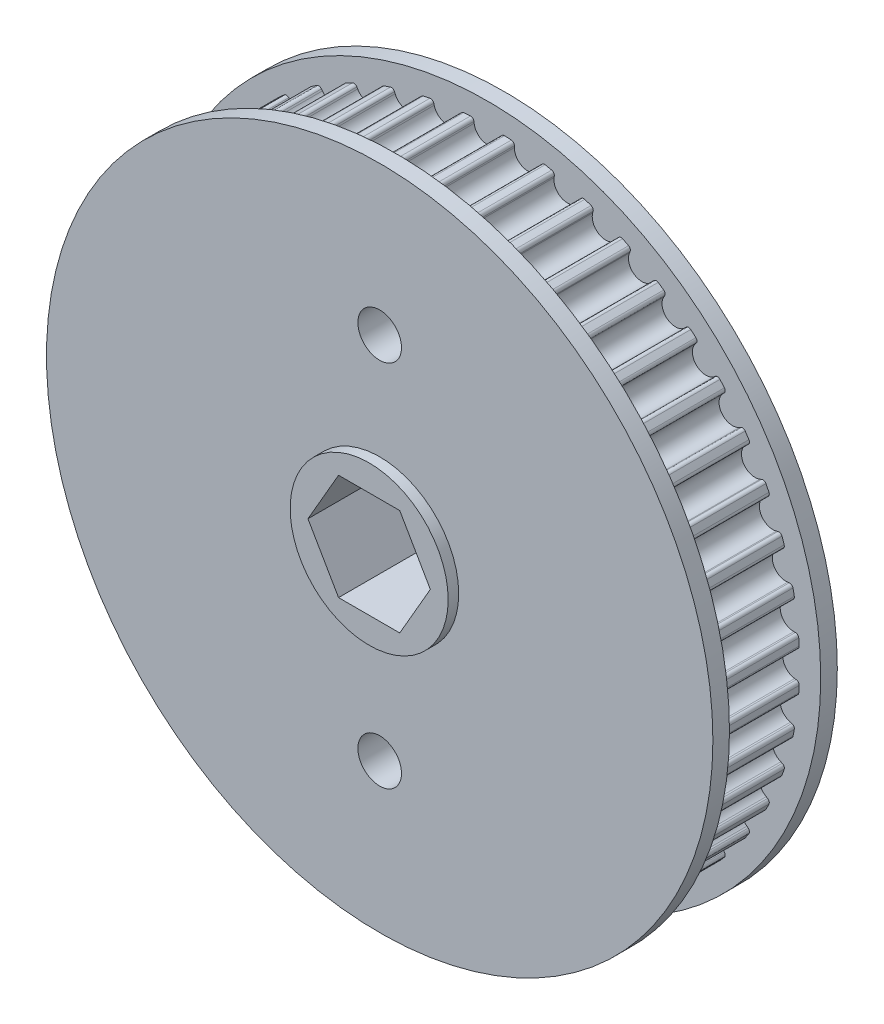
SolidWorks part; units mm, degrees
material "ABS"
ref_plane "Front Plane" through (0, 0, 0) normal (0, 0, 1) x (1, 0, 0)
ref_plane "Top Plane" through (0, 0, 0) normal (0, 1, 0) x (1, 0, 0)
ref_plane "Right Plane" through (0, 0, 0) normal (1, 0, 0) x (0, 0, -1)
sketch "Sketch2" plane through (0, 0, 0) normal (0, 0, 1) x (1, 0, 0)
  circle A0 centre (0, 0) radius 37.6245
  dimension "D1" = 75.2489
extrude "pulley" add sketch "Sketch2" along normal mid plane 11
sketch "tooth" plane through (0, 0, 0) normal (0, 0, 1) x (1, 0, 0)
  line L0 (0, 0) -> (0, 37.2245) construction
  line L1 (4.9887, 36.8887) -> (0, 37.2245) construction
  line L2 (4.9887, 36.8887) -> (0, 0) construction
  line L3 (-2.1327, 41.2601) -> (-1.6129, 37.0264)
  line L6 (2.1327, 41.2601) -> (1.6129, 37.0264)
  line L7 (-2.1327, 41.2601) -> (2.1327, 41.2601)
  arc A1 (-1.6129, 37.0264) -> (1.6129, 37.0264) centre (0, 37.2245) ccw
  arc A2 (0, 37.2245) -> (4.9887, 36.8887) centre (0, 0) cw construction
  circle A3 centre (4.9887, 36.8887) radius 1.625 construction
  dimension "D1" = 37.2245
  dimension "D2" = 3.25
  dimension "D3" = 5
  dimension "D4" = 7.702
  dimension "D5" = 14
extrude "cut tooth" cut sketch "tooth" against normal mid plane 11
fillet "blend tooth" radius 0.4 2 edges at (1.6817, 37.5869, 0) (-1.6817, 37.5869, 0)
pattern_circular "tooth pattern" count 48 over 360 about axis through (0, 0, 5.5) along (0, 0, -1) of "cut tooth", "blend tooth"
sketch "Sketch3" plane through (0, 0, 0) normal (0, 0, 1) x (1, 0, 0)
  circle A0 centre (0, 0) radius 40.1645
  circle A1 centre (0, 0) radius 37.6245 construction
  dimension "D1" = 2.54
extrude "sidewall" add sketch "Sketch3" along normal blind 2 from offset 5.5
mirror "mirror sidewall" about plane through (0, 0, 0) normal (0, 0, 1) of "sidewall"
chamfer "sidewall chamfer" [suppressed] distance 2.4 angle 10
sketch "Sketch5" plane through (0, 0, 0) normal (0, 0, 1) x (1, 0, 0)
  circle A0 centre (0, 0) radius 9.525
  dimension "D1" = 19.05
extrude "bearing spacer (Manual Suppress)" add sketch "Sketch5" along normal blind 8.77 and the other way blind 8.77
sketch "Sketch4" plane through (0, 0, 0) normal (0, 0, 1) x (1, 0, 0)
  line L1 (3.6882, 6.3881) -> (-3.6882, 6.3881)
  line L2 (-3.6882, 6.3881) -> (-7.3763, 0)
  line L3 (-7.3763, 0) -> (-3.6882, -6.3881)
  line L4 (-3.6882, -6.3881) -> (3.6882, -6.3881)
  line L5 (3.6882, -6.3881) -> (7.3763, 0)
  line L6 (7.3763, 0) -> (3.6882, 6.3881)
  circle A0 centre (0, 0) radius 6.3881 construction
  dimension "D1" = 12.7762
extrude "hex shaft" cut sketch "Sketch4" against normal mid plane 127
chamfer "chamfers" [suppressed] distance 0.254 angle 45
sketch "SK-VersaCut" plane through (0, 0, 0) normal (0, 0, 1) x (1, 0, 0)
  line B0 (6.3387, 23.6565) -> (5.299, 19.7762)
  line B1 (14.4772, 14.4772) -> (17.3177, 17.3177)
  line B2 (23.6565, 6.3387) -> (19.7762, 5.299)
  line B3 (19.7762, -5.299) -> (23.6565, -6.3387)
  line B4 (17.3177, -17.3177) -> (14.4772, -14.4772)
  line B5 (5.299, -19.7762) -> (6.3387, -23.6565)
  line B6 (-6.3387, -23.6565) -> (-5.299, -19.7762)
  line B7 (-14.4772, -14.4772) -> (-17.3177, -17.3177)
  line B8 (-23.6565, -6.3387) -> (-19.7762, -5.299)
  line B9 (-19.7762, 5.299) -> (-23.6565, 6.3387)
  line B10 (-17.3177, 17.3177) -> (-14.4772, 14.4772)
  line B11 (-5.299, 19.7762) -> (-6.3387, 23.6565)
  circle B12 centre (0, 23.8125) radius 2.2479
  arc B13 (5.9535, 18.5765) -> (13.1109, 14.4442) centre (0, 0) cw
  arc B14 (7.5904, 24.3458) -> (17.2889, 18.7464) centre (0, 0) cw
  arc B15 (5.9535, 18.5765) -> (5.299, 19.7762) centre (6.2559, 19.5198) cw
  arc B16 (13.1109, 14.4442) -> (14.4772, 14.4772) centre (13.7767, 15.1777) ccw
  arc B17 (17.2889, 18.7464) -> (17.3177, 17.3177) centre (16.6173, 18.0182) cw
  arc B18 (7.5904, 24.3458) -> (6.3387, 23.6565) centre (7.2956, 23.4001) ccw
  circle B19 centre (20.6222, 11.9062) radius 2.2479
  arc B20 (19.0645, 4.1323) -> (19.0645, -4.1323) centre (0, 0) cw
  arc B21 (24.8793, 5.5994) -> (24.8793, -5.5994) centre (0, 0) cw
  arc B22 (19.0645, 4.1323) -> (19.7762, 5.299) centre (20.0326, 4.3422) cw
  arc B23 (19.0645, -4.1323) -> (19.7762, -5.299) centre (20.0326, -4.3422) ccw
  arc B24 (24.8793, -5.5994) -> (23.6565, -6.3387) centre (23.9129, -5.3819) cw
  arc B25 (24.8793, 5.5994) -> (23.6565, 6.3387) centre (23.9129, 5.3819) ccw
  circle B26 centre (20.6222, -11.9063) radius 2.2479
  arc B27 (13.1109, -14.4442) -> (5.9535, -18.5765) centre (0, 0) cw
  arc B28 (17.2889, -18.7464) -> (7.5904, -24.3458) centre (0, 0) cw
  arc B29 (13.1109, -14.4442) -> (14.4772, -14.4772) centre (13.7767, -15.1777) cw
  arc B30 (5.9535, -18.5765) -> (5.299, -19.7762) centre (6.2559, -19.5198) ccw
  arc B31 (7.5904, -24.3458) -> (6.3387, -23.6565) centre (7.2956, -23.4001) cw
  arc B32 (17.2889, -18.7464) -> (17.3177, -17.3177) centre (16.6173, -18.0182) ccw
  circle B33 centre (0, -23.8125) radius 2.2479
  arc B34 (-5.9535, -18.5765) -> (-13.1109, -14.4442) centre (0, 0) cw
  arc B35 (-7.5904, -24.3458) -> (-17.2889, -18.7464) centre (0, 0) cw
  arc B36 (-5.9535, -18.5765) -> (-5.299, -19.7762) centre (-6.2559, -19.5198) cw
  arc B37 (-13.1109, -14.4442) -> (-14.4772, -14.4772) centre (-13.7767, -15.1777) ccw
  arc B38 (-17.2889, -18.7464) -> (-17.3177, -17.3177) centre (-16.6173, -18.0182) cw
  arc B39 (-7.5904, -24.3458) -> (-6.3387, -23.6565) centre (-7.2956, -23.4001) ccw
  circle B40 centre (-20.6222, -11.9063) radius 2.2479
  arc B41 (-19.0645, -4.1323) -> (-19.0645, 4.1323) centre (0, 0) cw
  arc B42 (-24.8793, -5.5994) -> (-24.8793, 5.5994) centre (0, 0) cw
  arc B43 (-19.0645, -4.1323) -> (-19.7762, -5.299) centre (-20.0326, -4.3422) cw
  arc B44 (-19.0645, 4.1323) -> (-19.7762, 5.299) centre (-20.0326, 4.3422) ccw
  arc B45 (-24.8793, 5.5994) -> (-23.6565, 6.3387) centre (-23.9129, 5.3819) cw
  arc B46 (-24.8793, -5.5994) -> (-23.6565, -6.3387) centre (-23.9129, -5.3819) ccw
  circle B47 centre (-20.6222, 11.9063) radius 2.2479
  arc B48 (-13.1109, 14.4442) -> (-5.9535, 18.5765) centre (0, 0) cw
  arc B49 (-17.2889, 18.7464) -> (-7.5904, 24.3458) centre (0, 0) cw
  arc B50 (-13.1109, 14.4442) -> (-14.4772, 14.4772) centre (-13.7767, 15.1777) cw
  arc B51 (-5.9535, 18.5765) -> (-5.299, 19.7762) centre (-6.2559, 19.5198) ccw
  arc B52 (-7.5904, 24.3458) -> (-6.3387, 23.6565) centre (-7.2956, 23.4001) cw
  arc B53 (-17.2889, 18.7464) -> (-17.3177, 17.3177) centre (-16.6173, 18.0182) ccw
sketch_block_instance "VersaKey-1"
sketch_block "Block1" parameters "D1"=47.625, "D2"=4.4958, "D3"=19.5072, "D4"=25.5016, "D6"=0.9906, "D5"=30
extrude "VersaKey (Manual Suppress)" [suppressed] cut sketch "SK-VersaCut" against normal through all both and the other way through all
sketch "Lightening Holes" plane through (0, 0, 0) normal (0, 0, 1) x (1, 0, 0)
  line L0 (-13.5587, 28.5643) -> (-3.9521, 11.9253)
  line L1 (3.9521, 11.9253) -> (13.5587, 28.5643)
  line L14 (0, 0) -> (-3.6662, 6.35) construction
  line L15 (0, 0) -> (0, 6.35) construction
  line L24 (0, 0) -> (3.6662, 6.35) construction
  line L25 (0, 6.35) -> (-3.6662, 6.35) construction
  line L26 (0, 6.35) -> (3.6662, 6.35) construction
  line L27 (-3.0943, 11.43) -> (3.0943, 11.43)
  line L28 (0, 6.35) -> (0, 11.43) construction
  line L29 (17.9581, 26.0243) -> (8.3515, 9.3853)
  line L30 (8.3515, 8.3947) -> (11.4458, 3.0353)
  line L31 (12.3037, 2.54) -> (31.5167, 2.54)
  line L32 (31.5167, -2.54) -> (12.3037, -2.54)
  line L33 (11.4458, -3.0353) -> (8.3515, -8.3947)
  line L34 (8.3515, -9.3853) -> (17.9581, -26.0243)
  line L35 (13.5587, -28.5643) -> (3.9521, -11.9253)
  line L36 (3.0943, -11.43) -> (-3.0943, -11.43)
  line L37 (-3.9521, -11.9253) -> (-13.5587, -28.5643)
  line L38 (-17.9581, -26.0243) -> (-8.3515, -9.3853)
  line L39 (-8.3515, -8.3947) -> (-11.4458, -3.0353)
  line L40 (-12.3037, -2.54) -> (-31.5167, -2.54)
  line L41 (-31.5167, 2.54) -> (-12.3037, 2.54)
  line L42 (-11.4458, 3.0353) -> (-8.3515, 8.3947)
  line L43 (-8.3515, 9.3853) -> (-17.9581, 26.0243)
  arc A3 (-13.0975, 29.9673) -> (13.0975, 29.9673) centre (0, 0) cw
  arc A4 (-3.0943, 11.43) -> (-3.9521, 11.9253) centre (-3.0943, 12.4206) cw
  arc A5 (3.0943, 11.43) -> (3.9521, 11.9253) centre (3.0943, 12.4206) ccw
  arc A6 (13.0975, 29.9673) -> (13.5587, 28.5643) centre (12.7008, 29.0596) cw
  arc A7 (-13.0975, 29.9673) -> (-13.5587, 28.5643) centre (-12.7008, 29.0596) ccw
  arc A72 (19.4037, 26.3264) -> (32.5012, 3.6409) centre (0, 0) cw
  arc A73 (19.4037, 26.3264) -> (17.9581, 26.0243) centre (18.816, 25.529) ccw
  arc A74 (8.3515, 8.3947) -> (8.3515, 9.3853) centre (9.2094, 8.89) cw
  arc A75 (32.5012, 3.6409) -> (31.5167, 2.54) centre (31.5167, 3.5306) cw
  arc A76 (32.5012, -3.6409) -> (19.4037, -26.3264) centre (0, 0) cw
  arc A77 (32.5012, -3.6409) -> (31.5167, -2.54) centre (31.5167, -3.5306) ccw
  arc A78 (11.4458, -3.0353) -> (12.3037, -2.54) centre (12.3037, -3.5306) cw
  arc A79 (19.4037, -26.3264) -> (17.9581, -26.0243) centre (18.816, -25.529) cw
  arc A80 (13.0975, -29.9673) -> (-13.0975, -29.9673) centre (0, 0) cw
  arc A81 (13.0975, -29.9673) -> (13.5587, -28.5643) centre (12.7008, -29.0596) ccw
  arc A82 (3.0943, -11.43) -> (3.9521, -11.9253) centre (3.0943, -12.4206) cw
  arc A83 (-13.0975, -29.9673) -> (-13.5587, -28.5643) centre (-12.7008, -29.0596) cw
  arc A84 (-19.4037, -26.3264) -> (-32.5012, -3.6409) centre (0, 0) cw
  arc A85 (-19.4037, -26.3264) -> (-17.9581, -26.0243) centre (-18.816, -25.529) ccw
  arc A86 (-8.3515, -8.3947) -> (-8.3515, -9.3853) centre (-9.2094, -8.89) cw
  arc A87 (-32.5012, -3.6409) -> (-31.5167, -2.54) centre (-31.5167, -3.5306) cw
  arc A88 (-32.5012, 3.6409) -> (-19.4037, 26.3264) centre (0, 0) cw
  arc A89 (-32.5012, 3.6409) -> (-31.5167, 2.54) centre (-31.5167, 3.5306) ccw
  arc A90 (-11.4458, 3.0353) -> (-12.3037, 2.54) centre (-12.3037, 3.5306) cw
  arc A91 (-19.4037, 26.3264) -> (-17.9581, 26.0243) centre (-18.816, 25.529) cw
  arc A92 (11.4458, 3.0353) -> (12.3037, 2.54) centre (12.3037, 3.5306) ccw
  arc A93 (8.3515, -8.3947) -> (8.3515, -9.3853) centre (9.2094, -8.89) ccw
  arc A94 (-3.0943, -11.43) -> (-3.9521, -11.9253) centre (-3.0943, -12.4206) ccw
  arc A95 (-11.4458, -3.0353) -> (-12.3037, -2.54) centre (-12.3037, -3.5306) ccw
  arc A96 (-8.3515, 8.3947) -> (-8.3515, 9.3853) centre (-9.2094, 8.89) ccw
  point P72 (0, 0)
  point P77 (0, 0)
  point P87 (0, 0)
  dimension "D4" = 32.7045
  dimension "D6" = 0.9906
  dimension "D5" = 2.54
  dimension "D7" = 60
  dimension "D1" = 6.35
  dimension "D3" = 5.08
  dimension "D2" = 6
extrude "Lightening Holes (Man Suppress)" [suppressed] cut sketch "Lightening Holes" against normal through all both and the other way through all
sketch "Sketch6" plane through (0, 0, 0) normal (0, 0, 1) x (1, 0, 0)
  line L0 (0, 11.9148) -> (0, 0) construction
  line L1 (0, 0) -> (0, -11.9148) construction
  arc A1 (0, 11.9148) -> (0, -11.9148) centre (0, 0) cw construction
  arc A2 (0, 11.9148) -> (0, -11.9148) centre (0, 0) ccw construction
  text T0 "46"
extrude "4419" [suppressed] cut sketch "Sketch6" along normal blind 2.54 from offset 6.992
sketch "Sketch7" plane through (0, 0, 7.5) normal (0, 0, 1) x (1, 0, 0)
  circle A0 centre (0, 0) radius 50.8
  dimension "D1" = 101.6
extrude "Cut-Extrude2" [suppressed] cut sketch "Sketch7" against normal blind 7.5
sketch "Sketch8" plane through (0, 0, -7.5) normal (0, 0, -1) x (-1, 0, 0)
  circle A0 centre (0, 0) radius 17.4625 construction
  text T0 "48\r\n"
  dimension "D1" = 34.925
extrude "number of teeth" cut sketch "Sketch8" against normal blind 3.175
sketch "Sketch9" plane through (0, 0, -7.5) normal (0, 0, -1) x (-1, 0, 0)
  line L0 (0, 0) -> (0, -22.225) construction
  line L1 (0, 0) -> (0, 22.225) construction
  circle A0 centre (0, -22.225) radius 2.6289
  circle A1 centre (0, 22.225) radius 2.6289
  dimension "D1" = 5.2578
  dimension "D4" = 5.2578
  dimension "D2" = 22.225
  dimension "D3" = 22.225
extrude "Cut-Extrude4" cut sketch "Sketch9" against normal through all
sketch "Sketch10" plane through (0, 0, -7.5) normal (0, 0, -1) x (-1, 0, 0)
  circle A0 centre (0, -22.225) radius 3.9688
  dimension "D1" = 7.9375
extrude "Cut-Extrude5" cut sketch "Sketch10" against normal blind 4.7625
sketch "Sketch11" plane through (0, 0, -7.5) normal (0, 0, -1) x (-1, 0, 0)
  line L1 (-2.7496, 17.4625) -> (2.7496, 17.4625)
  line L2 (2.7496, 17.4625) -> (5.4993, 22.225)
  line L3 (5.4993, 22.225) -> (2.7496, 26.9875)
  line L4 (2.7496, 26.9875) -> (-2.7496, 26.9875)
  line L5 (-2.7496, 26.9875) -> (-5.4993, 22.225)
  line L6 (-5.4993, 22.225) -> (-2.7496, 17.4625)
  circle A0 centre (0, 22.225) radius 4.7625 construction
  dimension "D1" = 9.525
extrude "Cut-Extrude6" cut sketch "Sketch11" against normal blind 6.35
equation "\"INPUT_pulley_teeth\"= 48"
equation "\"pulley_c2c\"= 5mm"
equation "\"pulley_teeth_deg\"= 360 / \"INPUT_pulley_teeth\""
equation "\"pulley_radius\"= ( \"pulley_c2c\" / ( 2 * cos ( \"iso_half_angle\" ) ) ) - 1mm"
equation "\"iso_half_angle\"= ( 180 - \"pulley_teeth_deg\" ) / 2"
equation "\"D1@tooth\" = \"pulley_radius\""
equation "\"pulley_tooth_dia\"= 3.25mm"
equation "\"D3@tooth\"=\"pulley_c2c\""
equation "\"D2@tooth\"=\"pulley_tooth_dia\""
equation "\"D1@Sketch2\"=2* \"pulley_radius\"+\"pulley_tooth_offset\""
equation "\"pulley_tooth_offset\"= .8mm"
equation "\"D1@tooth pattern\" = \"INPUT_pulley_teeth\""
equation "\"INPUT_pulley_belt_9_or_15_(unitless)\"= 9"
equation "\"D1@pulley\"=\"pulley_width\""
equation "\"D19@sidewall\" =  ( \"pulley_width\" / 2 ) "
equation "\"D1@sidewall\"=\"pulley_sidewall_thick\""
equation "\"pulley_width\"= IIF ( \"INPUT_pulley_belt_9_or_15_(unitless)\" = 9 , 11mm , 17mm )"
equation "\"D1@cut tooth\"=\"pulley_width\""
equation "\"D1@sidewall chamfer\" = 2.4mm"
equation "\"D4@Lightening Holes\"=\"pulley_radius\"-\"pulley_tooth_dia\"-.05"
equation "\"D1@bearing spacer (Manual Suppress)\" = 0.05 +  ( \"pulley_width\" / 2 )  + \"pulley_sidewall_thick\""
equation "\"D2@bearing spacer (Manual Suppress)\" = 0.05 +  ( \"pulley_width\" / 2 )  + \"pulley_sidewall_thick\""
equation "\"pulley_sidewall_thick\"= 2mm"
equation "\"D19@4419\"=(\"pulley_width\" / 2) +\"pulley_sidewall_thick\" - 0.02"
equation "\"rad_len\" = \"INPUT_pulley_teeth\" * \"pulley_c2c\""
